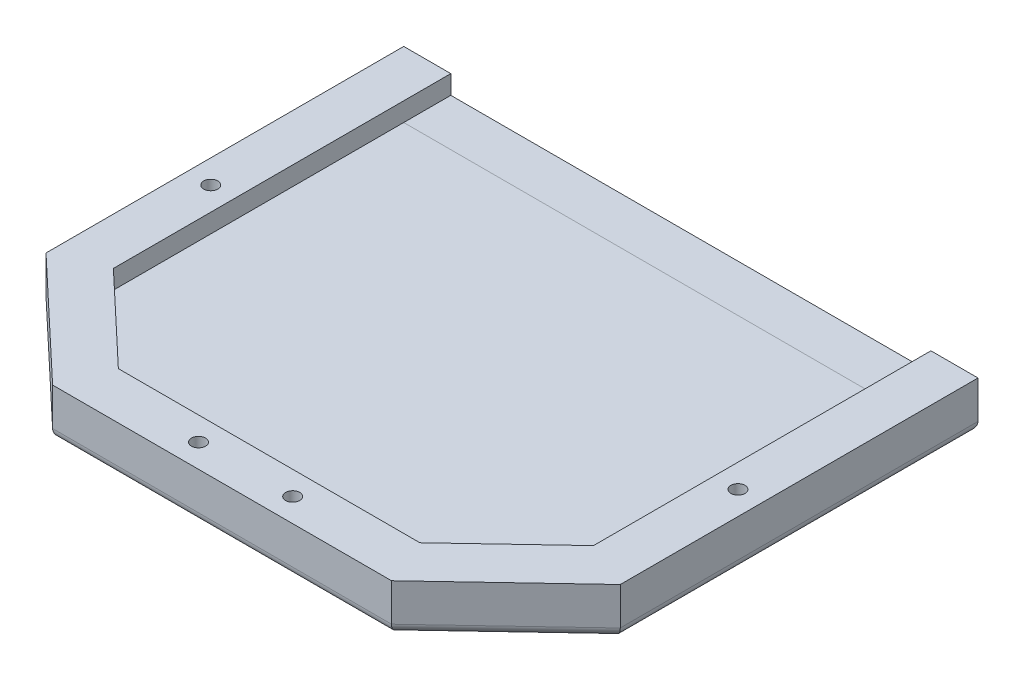
SolidWorks part; units mm, degrees
ref_plane "Płaszczyzna przednia" through (0, 0, 0) normal (0, 0, 1) x (1, 0, 0)
ref_plane "Płaszczyzna górna" through (0, 0, 0) normal (0, 1, 0) x (1, 0, 0)
ref_plane "Płaszczyzna prawa" through (0, 0, 0) normal (1, 0, 0) x (0, 0, -1)
sketch "Szkic1" plane through (0, 0, 0) normal (0, 1, 0) x (1, 0, 0)
  line L0 (-24.7421, -43.1447) -> (36.2579, -43.1447)
  line L1 (36.2579, -43.1447) -> (36.2579, -81.1447)
  line L2 (36.2579, -81.1447) -> (23.7579, -92.9447)
  line L3 (23.7579, -92.9447) -> (-12.2421, -92.9447)
  line L4 (-24.7421, -43.1447) -> (-24.7421, -81.1447)
  line L5 (-24.7421, -81.1447) -> (-12.2421, -92.9447)
  dimension "D1" = 61
  dimension "D2" = 38
  dimension "D3" = 11.8
  dimension "D4" = 12.5
  dimension "D5" = 36
  dimension "D6" = 38
  dimension "D7" = 11.8
extrude "Dodanie-wyciągnięcie1" add sketch "Szkic1" along normal blind 3
sketch "Szkic2" plane through (0, 3, 0) normal (0, 1, 0) x (1, 0, 0)
  line L0 (-19.7421, -48.1447) -> (31.2579, -48.1447)
  line L1 (36.2579, -43.1447) -> (-24.7421, -43.1447) construction
  line L2 (36.2579, -81.1447) -> (36.2579, -43.1447) construction
  line L3 (-19.7421, -48.1447) -> (-19.7421, -78.9888)
  line L7 (31.2579, -48.1447) -> (31.2579, -78.9888)
  line L9 (-19.7421, -78.9888) -> (-10.2549, -87.9447)
  line L10 (-24.7421, -81.1447) -> (-12.2421, -92.9447) construction
  line L11 (-10.2549, -87.9447) -> (21.7707, -87.9447)
  line L12 (-12.2421, -92.9447) -> (23.7579, -92.9447) construction
  line L13 (31.2579, -78.9888) -> (21.7707, -87.9447)
  line L15 (23.7579, -92.9447) -> (36.2579, -81.1447) construction
  dimension "D1" = 51
  dimension "D2" = 5
  dimension "D3" = 5
  dimension "D4" = 5
  dimension "D5" = 5
  dimension "D6" = 5
  dimension "D8" = 5
extrude "Wyciągnięcie-cienka ścianka2" add sketch "Szkic2" along normal blind 2 thin thin type one direction wall 5
sketch "Szkic3" plane through (0, 5, 0) normal (0, 1, 0) x (1, 0, 0)
  line L0 (-12.2421, -92.9447) -> (23.7579, -92.9447) construction
  line L1 (-24.7421, -43.1447) -> (-24.7421, -81.1447) construction
  line L2 (36.2579, -81.1447) -> (36.2579, -43.1447) construction
  circle A0 centre (0.7579, -90.4447) radius 0.75
  circle A1 centre (10.7579, -90.4447) radius 0.75
  circle A2 centre (-22.2421, -66.1447) radius 0.75
  circle A3 centre (33.7579, -66.1447) radius 0.75
  dimension "D3" = 1.5
  dimension "D4" = 1.5
  dimension "D9" = 1.5
  dimension "D10" = 1.5
  dimension "D1" = 10
  dimension "D2" = 13
  dimension "D5" = 2.5
  dimension "D6" = 2.5
  dimension "D7" = 2.5
  dimension "D8" = 2.5
  dimension "D11" = 15
  dimension "D12" = 15
extrude "Wytnij-wyciągnięcie1" cut sketch "Szkic3" against normal blind 40 and the other way blind 27
fillet "Zaokrąglenie2" radius 1 10 edges at (-18.4921, 0, 87.0447) (5.7579, 0, 92.9447) (30.0079, 0, 87.0447) (36.2579, 0, 62.1447) (5.7579, 0, 43.1447) (-24.7421, 0, 62.1447) (0.7579, 0, 89.6947) (10.7579, 0, 89.6947) (-22.2421, 0, 65.3947) (33.7579, 0, 65.3947)
sketch "Szkic4" plane through (0, 3, 0) normal (0, 1, 0) x (1, 0, 0)
  line L0 (31.2579, -48.1447) -> (31.2579, -43.1447)
  line L1 (36.2579, -43.1447) -> (-24.7421, -43.1447) construction
  line L2 (-19.7421, -48.1447) -> (-19.7421, -43.1447)
  line L3 (-19.7421, -43.1447) -> (31.2579, -43.1447)
  line M1 (31.2579, -48.1447) -> (-19.7421, -48.1447)
extrude "Wytnij-wyciągnięcie2" cut sketch "Szkic4" against normal blind 0.0001 and the other way through all contours L3 L2 L0 M1 region at (5.7579, 3, 45.6447)
